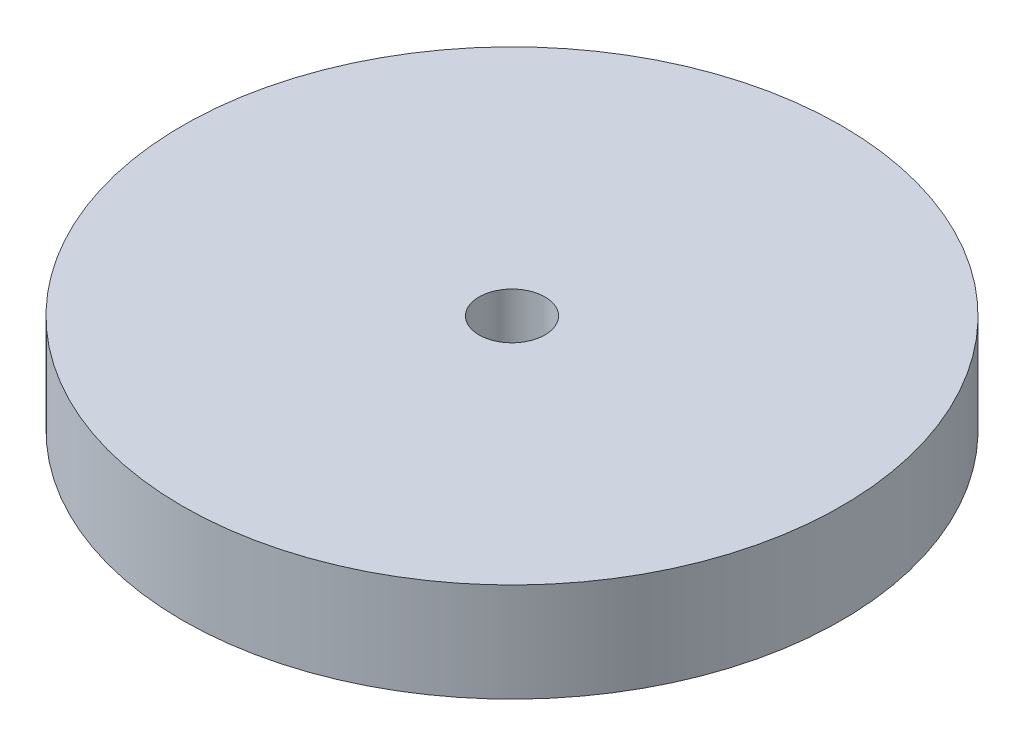
SolidWorks part; units mm, degrees
ref_plane "Front Plane" through (0, 0, 0) normal (0, 0, 1) x (1, 0, 0)
ref_plane "Top Plane" through (0, 0, 0) normal (0, 1, 0) x (1, 0, 0)
ref_plane "Right Plane" through (0, 0, 0) normal (1, 0, 0) x (0, 0, -1)
sketch "Sketch1" plane through (0, 0, 0) normal (0, 1, 0) x (1, 0, 0)
  circle A0 centre (0, 0) radius 50
  dimension "D1" = 100
sketch "Sketch2" plane through (0, 0, 0) normal (0, 1, 0) x (1, 0, 0)
  circle A0 centre (0, 0) radius 5
extrude "Boss-Extrude1" add sketch "Sketch1" along normal blind 7.5 and the other way blind 7.5 contours A0
extrude "Cut-Extrude2" cut sketch "Sketch2" against normal through all both and the other way through all
sketch "Sketch5" plane through (0, 0, 0) normal (1, 0, 0) x (0, 0, -1)
  line L0 (0, 0) -> (0, 11.8457) construction
  line L1 (0, 0) -> (0, -8.9291) construction
  point P3 (0, 0)
  point P5 (0, 0)
